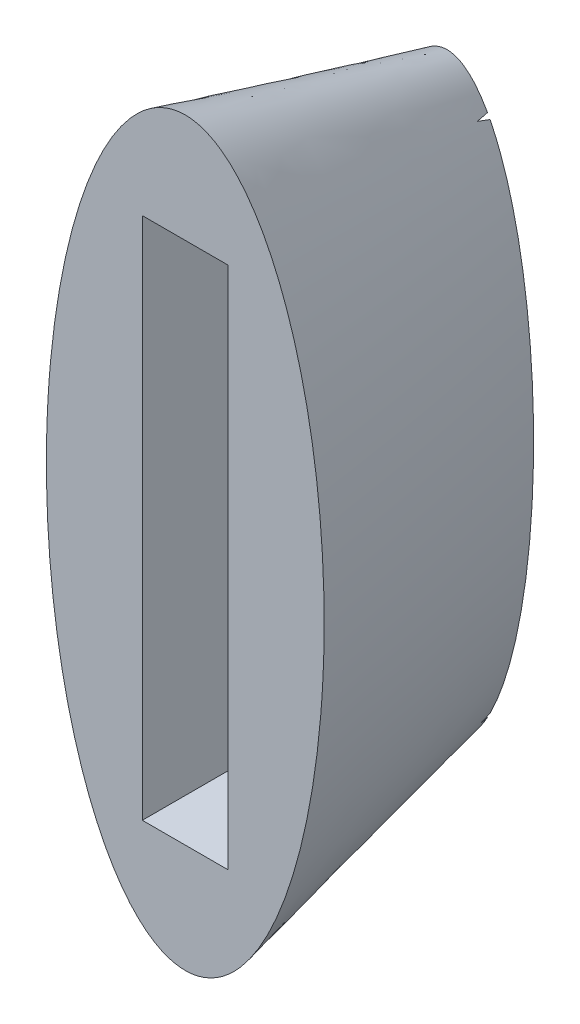
SolidWorks part; units mm, degrees
ref_plane "Front Plane" through (0, 0, 0) normal (0, 0, 1) x (1, 0, 0)
ref_plane "Top Plane" through (0, 0, 0) normal (0, 1, 0) x (1, 0, 0)
ref_plane "Right Plane" through (0, 0, 0) normal (1, 0, 0) x (0, 0, -1)
sketch "Sketch1" plane through (0, 0, 0) normal (0, 0, 1) x (1, 0, 0)
  ellipse E0 centre (0, 0) end of major axis (0, 17.6875) minor radius 6.6301
  dimension "D1" = 13.2601
  dimension "D2" = 35.375
ref_plane "Plane1" through (0, 0, -12.5) normal (0, 0, 1) x (1, 0, 0)
sketch "Sketch2" plane through (0, 0, -12.5) normal (0, 0, 1) x (1, 0, 0)
  ellipse E0 centre (0, 0) end of major axis (0, 14.1372) minor radius 4.1301
  dimension "D1" = 28.2744
  dimension "D2" = 8.2601
loft "Loft2" add profiles "Sketch2", "Sketch1" connector at (-4.0828, 2.1326, -12.5) connector at (-6.6273, -0.5111, 0)
sketch "Sketch6" plane through (0, 0, 0) normal (0, 0, 1) x (1, 0, 0)
  line L1 (-2.05, 12.5) -> (2.05, 12.5)
  line L2 (-2.05, 12.5) -> (-2.05, -12.5)
  line L3 (-2.05, -12.5) -> (2.05, -12.5)
  line L4 (2.05, 12.5) -> (2.05, -12.5)
  line L5 (-2.05, 12.5) -> (2.05, -12.5) construction
  line L6 (-2.05, -12.5) -> (2.05, 12.5) construction
  point P0 (0, 0)
  dimension "D1" = 4.1
  dimension "D2" = 25
extrude "Cut-Extrude2" cut sketch "Sketch6" against normal blind 20
